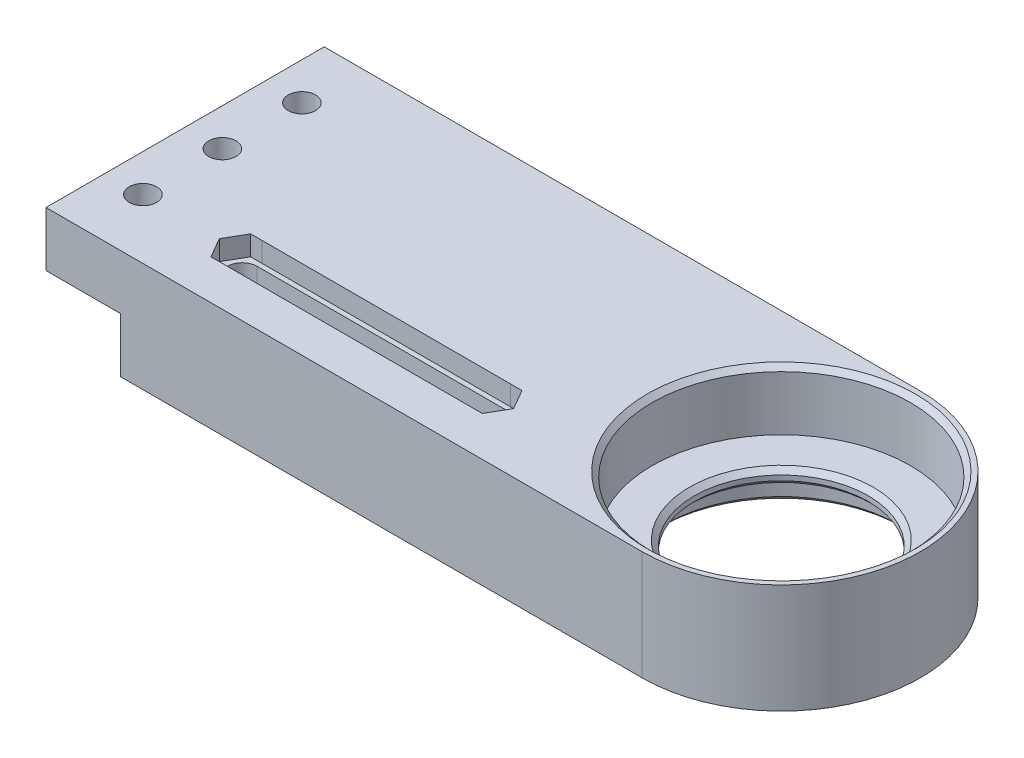
SolidWorks part; units mm, degrees
note: The reader was unsure of these and kept them because the rebuilt part matched: shared geometry of "草图8<3>".
ref_plane "Front" through (0, 0, 0) normal (0, 0, 1) x (1, 0, 0)
ref_plane "Top" through (0, 0, 0) normal (0, 1, 0) x (1, 0, 0)
ref_plane "Right" through (0, 0, 0) normal (1, 0, 0) x (0, 0, -1)
sketch "草图1" plane through (0, 0, 0) normal (0, 1, 0) x (1, 0, 0)
  line L0 (-128.7916, 0) -> (62.2219, 0) construction
  line L1 (0, 56.2704) -> (0, -41.1981) construction
  line L3 (0, 28) -> (-120, 28)
  line L4 (0, 28) -> (0, -28) construction
  line L5 (0, -28) -> (-120, -28)
  line L6 (-120, 28) -> (-120, -28)
  arc A0 (0, 28) -> (0, -28) centre (0, 0) cw
  dimension "D1" = 120
  dimension "D2" = 28
  dimension "D3" = 56
extrude "凸台-拉伸1" add sketch "草图1" along normal blind 22
sketch "草图2" plane through (0, 0, 28) normal (0, 0, 1) x (1, 0, 0)
  line L1 (-120, 0) -> (-105, 0)
  line L2 (-120, 0) -> (-120, 11)
  line L3 (-120, 11) -> (-105, 11)
  line L4 (-105, 0) -> (-105, 11)
  dimension "D1" = 11
  dimension "D2" = 15
extrude "切除-拉伸1" cut sketch "草图2" against normal up to next
sketch "草图3" plane through (0, 22, 0) normal (0, 1, 0) x (1, 0, 0)
  circle A0 centre (0, 0) radius 26
  dimension "D1" = 52
extrude "切除-拉伸2" cut sketch "草图3" against normal blind 12
sketch "草图4" plane through (0, 10, 0) normal (0, 1, 0) x (1, 0, 0)
  circle A0 centre (0, 0) radius 17.5
  dimension "D1" = 35
extrude "切除-拉伸3" cut sketch "草图4" against normal up to next
sketch "草图5" plane through (0, 0, 0) normal (0, -1, 0) x (1, 0, 0)
  circle A0 centre (0, 0) radius 23.5
  dimension "D1" = 47
extrude "切除-拉伸4" cut sketch "草图5" against normal blind 7
chamfer "倒角1" distance 1 angle 45 4 edges at (0, 22, 26) (0, 0, -23.5) (0, 7, -17.5) (0, 10, 17.5)
sketch "草图6" plane through (0, 22, 0) normal (0, 1, 0) x (1, 0, 0)
  line L0 (-112.5, 37.393) -> (-112.5, -44.722) construction
  line L1 (-118.8522, 0) -> (50.1642, 0) construction
  line L2 (-120, 28) -> (-120, -28) construction
  circle A0 centre (-112.5, 0) radius 2.75
  circle A1 centre (-112.5, 16) radius 2.75
  circle A2 centre (-112.5, -16) radius 2.75
  point P7 (-112.5, 0)
  dimension "D2" = 5.5
  dimension "D3" = 5.5
  dimension "D1" = 7.5
  dimension "D4" = 16
extrude "切除-拉伸5" cut sketch "草图6" against normal up to next
sketch "草图7" plane through (0, 0, 28) normal (0, 0, 1) x (1, 0, 0)
  line L0 (-120, 22) -> (0, 22) construction
  line L1 (-40, 22) -> (28, 22)
  line L2 (-40, 22) -> (-40, 15) construction
  line L3 (-40, 15) -> (28, 15)
  line L4 (28, 22) -> (28, 15)
  line L5 (28, 0) -> (28, 22) construction
  line L6 (0, 22) -> (0, 0) construction
  line L7 (-40, 15) -> (-56.7697, 22)
  line L8 (-56.7697, 22) -> (-40, 22)
  dimension "D1" = 7
  dimension "D2" = 40
extrude "切除-拉伸6" [suppressed] cut sketch "草图7" against normal up to next
sketch "草图8" plane through (0, 22, 0) normal (0, 1, 0) x (1, 0, 0)
  line L0 (-112.5, -16) -> (-26.2554, -16) construction
  line L1 (-92.5, -12) -> (-42.5, -12)
  line L2 (-42.5, -19) -> (-92.5, -19)
  line L3 (-42.5, -19) -> (-42.5, -13) construction
  line L4 (-42.5, -13) -> (-92.5, -13)
  line L5 (-92.5, -19) -> (-92.5, -13) construction
  line L6 (-42.5, -19) -> (-92.5, -13) construction
  line L7 (-42.5, -13) -> (-92.5, -19) construction
  line L8 (-92.5, -20) -> (-42.5, -20)
  line L9 (-94.8084, -12.0018) -> (-92.5, -12)
  line L10 (-97.1167, -16) -> (-94.8084, -19.9982)
  line L15 (-94.8084, -12.0018) -> (-97.1167, -16)
  line L16 (-87.8833, -16) -> (-90.1916, -12.0018) [skipped]
  line L17 (-90.1916, -19.9982) -> (-87.8833, -16) [skipped]
  line L18 (-90.1916, -12.0018) -> (-94.8084, -12.0018) [skipped]
  line L19 (-94.8084, -19.9982) -> (-90.1916, -19.9982) [skipped]
  line L20 (-94.8084, -19.9982) -> (-92.5, -20)
  line L21 (-67.5, -10.0591) -> (-67.5, -23.3832) construction
  line L22 (-40.1916, -19.9982) -> (-42.5, -20)
  line L23 (-40.1916, -12.0018) -> (-42.5, -12)
  line L24 (-40.1916, -12.0018) -> (-37.8833, -16)
  line L25 (-37.8833, -16) -> (-40.1916, -19.9982)
  arc A0 (-92.5, -13) -> (-92.5, -19) centre (-92.5, -16) ccw
  arc A1 (-42.5, -13) -> (-42.5, -19) centre (-42.5, -16) cw
  circle A2 centre (-92.5, -16) radius 3.9982 construction
  point P3 (-67.5, -16)
  dimension "D4" = 8
  dimension "D1" = 6
  dimension "D2" = 20
  dimension "D3" = 50
  dimension "D5" = 7.9964
  dimension "D6" = 4.6167
extrude "切除-拉伸7" cut sketch "草图8" against normal up to next contours A1 L4 A0 L2
extrude "切除-拉伸8" cut sketch "草图8<3>" against normal blind 4
sketch "草图8<3>" plane through (0, 22, 0) normal (0, 1, 0) x (1, 0, 0) same geometry as "草图8"
